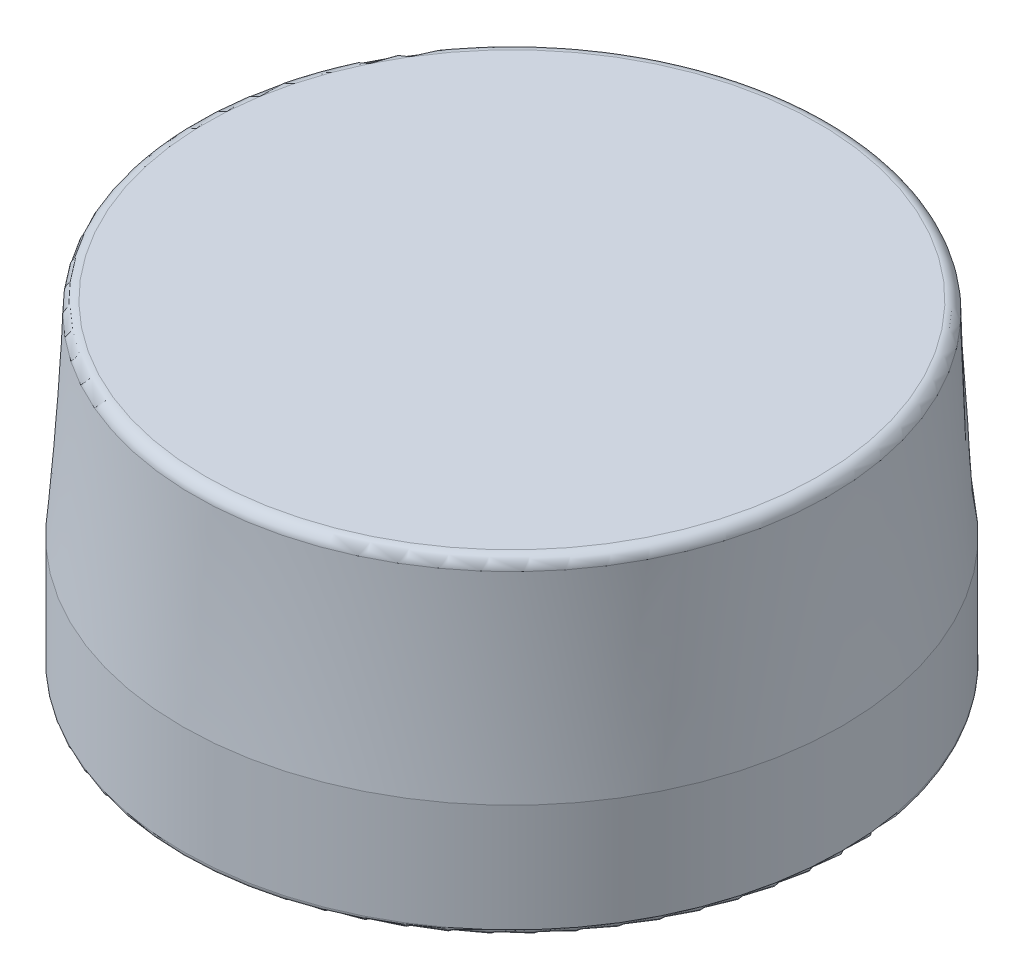
SolidWorks part; units mm, degrees
ref_plane "Front Plane" through (0, 0, 0) normal (0, 0, 1) x (1, 0, 0)
ref_plane "Top Plane" through (0, 0, 0) normal (0, 1, 0) x (1, 0, 0)
ref_plane "Right Plane" through (0, 0, 0) normal (1, 0, 0) x (0, 0, -1)
sketch "Sketch33" plane through (0, 0, 0) normal (0, 1, 0) x (1, 0, 0)
  circle A0 centre (0, 0) radius 27.9
  circle A1 centre (0, 0) radius 29
  circle A2 centre (0, 0) radius 26
extrude "Boss-Extrude6" add sketch "Sketch33" along normal blind 23 contours A0 A2 region at (-27.1109, 0, 0)
extrude "Boss-Extrude7" add sketch "Sketch33<6>" against normal blind 5 separate body contours A1 A0 region at (-28.1798, 0, 0)
sketch "Sketch33<6>" plane through (0, 0, 0) normal (0, 1, 0) x (1, 0, 0) same geometry as "Sketch33"
extrude "Boss-Extrude9" add sketch "Sketch33<8>" along normal blind 5 contours A1 A0 region at (-28.1798, 0, 0)
sketch "Sketch33<8>" plane through (0, 0, 0) normal (0, 1, 0) x (1, 0, 0) same geometry as "Sketch33"
extrude "Boss-Extrude10" add sketch "Sketch33<9>" along normal blind 1 from offset 22 contours A2 | A0 A2 region at (-27.1109, 0, 0) region at (0, 0, 0)
sketch "Sketch33<9>" plane through (0, 0, 0) normal (0, 1, 0) x (1, 0, 0) same geometry as "Sketch33"
loft "Loft2" add section edge at (0, 23, 27.9) section edge at (0, 5, 29) connector at (27.7795, 23, 2.5907) connector at (27.9087, 5, 7.8805)
sketch "Sketch36" plane through (0, 5, 0) normal (0, -1, 0) x (1, 0, 0)
  circle A0 centre (0, 0) radius 26
extrude "Cut-Extrude1" cut sketch "Sketch36" against normal blind 17
fillet "Fillet1" radius 1 1 edges at (0, 23, 27.9)
fillet "Fillet2" radius 0.5 2 edges at (0, -5, 29) (0, -5, 27.9)
